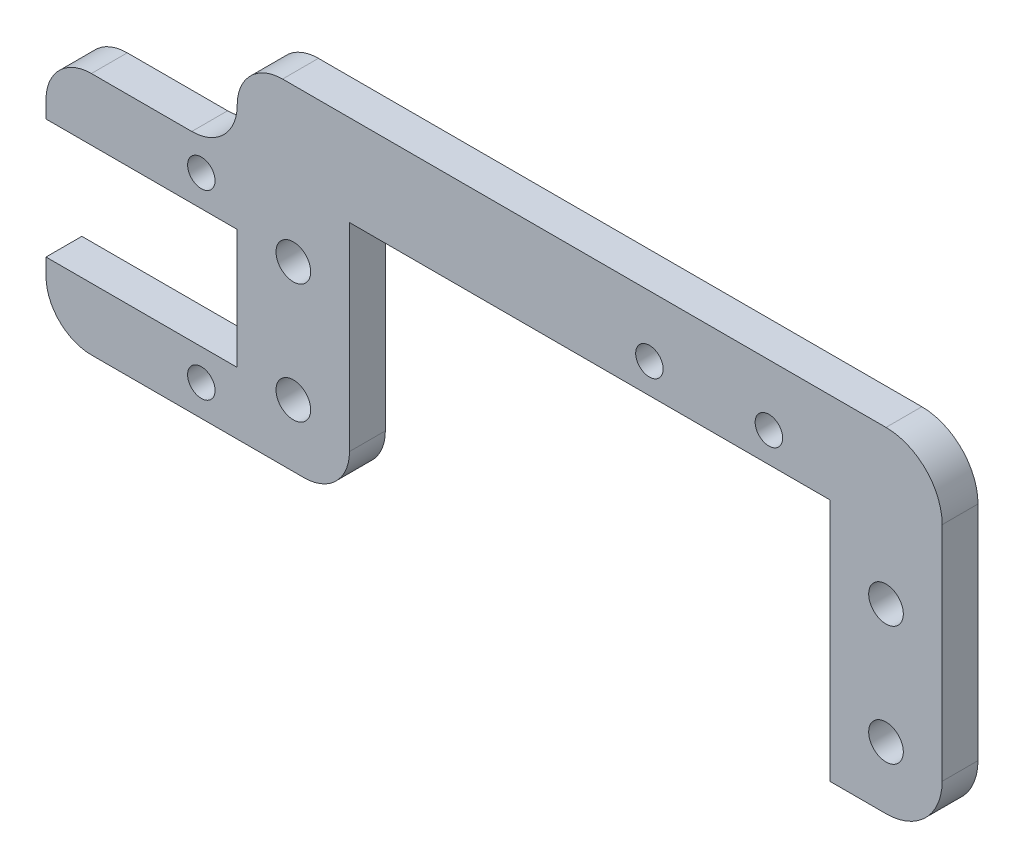
SolidWorks part; units mm, degrees
material "ABS"
ref_plane "Face" through (0, 0, 0) normal (0, 0, 1) x (1, 0, 0)
ref_plane "Dessus" through (0, 0, 0) normal (0, 1, 0) x (1, 0, 0)
ref_plane "Droite" through (0, 0, 0) normal (1, 0, 0) x (0, 0, -1)
sketch "Sketch10" plane through (0, 0, 0) normal (0, 0, 1) x (1, 0, 0)
  line L7 (17.4, 10.2) -> (57.6, 10.2)
  line L8 (57.6, 10.2) -> (57.6, -10.2)
  line L9 (57.6, -10.2) -> (67, -10.2)
  line L10 (8, 5) -> (-8, 5)
  line L11 (-8, 5) -> (-8, 10.2)
  line L15 (-8, -10.2) -> (-8, -5)
  line L16 (-8, -5) -> (8, -5)
  line L17 (8, -5) -> (8, 5)
  line L18 (-8, -10.2) -> (17.4, -10.2)
  line L19 (17.4, -10.2) -> (17.4, 10.2)
  line L20 (-8, 10.2) -> (8, 10.2)
  line L21 (8, 10.2) -> (8, 17.8)
  line L22 (8, 17.8) -> (67, 17.8)
  line L23 (67, -10.2) -> (67, 17.8)
  dimension "D1" = 5.2
  dimension "D2" = 20.4
  dimension "D3" = 5.2
  dimension "D4" = 40.2
  dimension "D5" = 9.4
  dimension "D6" = 12.8
  dimension "D7" = 20.4
  dimension "D8" = 16
  dimension "D9" = 59
extrude "Boss-Extrude7" add sketch "Sketch10" against normal blind 3
sketch "Sketch11" plane through (0, 0, 0) normal (0, 0, -1) x (-1, 0, 0)
  circle A0 centre (-62.3, -5) radius 1.45
  circle A4 centre (-12.7, -5) radius 1.45
  circle A5 centre (-12.7, 5) radius 1.45
  circle A6 centre (-62.3, 5) radius 1.45
  dimension "D1" = 4.7
  dimension "D2" = 5.2
  dimension "D3" = 2.9
  dimension "D4" = 2
  dimension "D5" = 2
sketch "Sketch12" plane through (0, 0, 0) normal (0, 0, -1) x (-1, 0, 0)
  circle A0 centre (-52.5, 12.7) radius 1.15
  circle A2 centre (-42.5, 12.7) radius 1.15
  dimension "D3" = 2.3
  dimension "D1" = 5.1
  dimension "D2" = 2.5
  dimension "D4" = 2
extrude "Cut-Extrude3" cut sketch "Sketch12" along normal through all
extrude "Cut-Extrude4" cut sketch "Sketch11" along normal through all
sketch "Sketch13" plane through (0, 0, 0) normal (0, 0, 1) x (1, 0, 0)
  circle A0 centre (5, 7.6) radius 1.15
  circle A2 centre (5, -7.6) radius 1.15
  dimension "D2" = 2.6
  dimension "D3" = 2.3
  dimension "D1" = 3
  dimension "D4" = 2
extrude "Cut-Extrude5" cut sketch "Sketch13" against normal through all
fillet "Fillet1" radius 4.7 2 edges at (67, -10.2, -1.5) (67, 17.8, -1.5)
fillet "Fillet2" radius 3.8 5 edges at (17.4, -10.2, -1.5) (-8, -10.2, -1.5) (8, 17.8, -1.5) (8, 10.2, -1.5) (-8, 10.2, -1.5)
